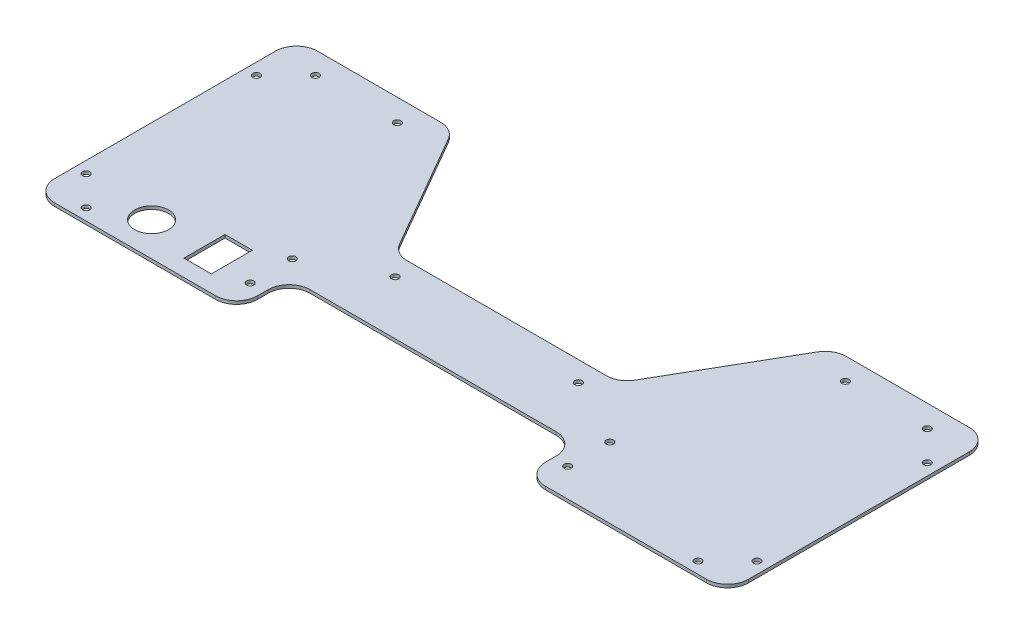
SolidWorks part; units mm, degrees
material "Alliage 1060"
ref_plane "Front" through (0, 0, 0) normal (0, 0, 1) x (1, 0, 0)
ref_plane "Top" through (0, 0, 0) normal (0, 1, 0) x (1, 0, 0)
ref_plane "Right" through (0, 0, 0) normal (1, 0, 0) x (0, 0, -1)
sketch "Esquisse1" plane through (0, 0, 0) normal (0, 1, 0) x (1, 0, 0)
  line L0 (0, 0) -> (0, 120) construction
  line L1 (-165, 120) -> (165, 120) construction
  line L2 (-165, 120) -> (-165, -30) construction
  line L3 (-165, -30) -> (-68.5, -30)
  line L4 (165, 120) -> (165, -30) construction
  line L5 (-165, -30) -> (-165, 90)
  line L6 (-165, 90) -> (-93.5278, 90) construction
  line L7 (-93.5278, 90) -> (-56, 25) construction
  line L8 (-56, 25) -> (56, 25) construction
  line L9 (56, 25) -> (93.5278, 90) construction
  line L10 (93.5278, 90) -> (165, 90) construction
  line L11 (165, 90) -> (165, -30)
  line L12 (-68.5, -30) -> (-68.5, -5)
  line L13 (-68.5, -5) -> (68.5, -5)
  line L14 (68.5, -5) -> (68.5, -30)
  line L15 (68.5, -30) -> (165, -30)
  line L16 (-165, 90) -> (-165, 95)
  line L17 (-165, 95) -> (-90.641, 95)
  line L18 (-90.641, 95) -> (-53.1132, 30)
  line L19 (-53.1132, 30) -> (53.1132, 30)
  line L20 (53.1132, 30) -> (90.641, 95)
  line L21 (90.641, 95) -> (165, 95)
  line L22 (165, 95) -> (165, 90)
  line L23 (-93.5278, 90) -> (-93.5278, 95) construction
  line L24 (-93.5278, 90) -> (-89.1976, 92.5) construction
  line L25 (-53.1132, 30) -> (-53.1132, 25) construction
  point P7 (0, 25)
  point P16 (0, -5)
  dimension "D1" = 120
  dimension "D5" = 30
  dimension "D2" = 120
  dimension "D3" = 330
  dimension "D4" = 150
  dimension "D6" = 65
  dimension "D7" = 56
  dimension "D8" = 25
  dimension "D9" = 137
  dimension "D10" = 5
extrude "Boss.-Extru.1" add sketch "Esquisse1" along normal blind 1.5
fillet "Congé2" radius 10 12 edges at (-165, 0.75, 30) (68.5, 0.75, 30) (68.5, 0.75, 5) (-68.5, 0.75, 5) (-68.5, 0.75, 30) (165, 0.75, 30) (90.641, 0.75, -95) (165, 0.75, -95) (53.1132, 0.75, -30) (-53.1132, 0.75, -30) (-90.641, 0.75, -95) (-165, 0.75, -95)
hole_wizard "Dégagement M31" positions "Esquisse2" profile "Esquisse3" hole size "M3" standard "Ansi Metric" end condition through all
sketch "Esquisse2" plane through (0, 1.5, 0) normal (0, 1, 0) x (1, 0, 0)
  line L1 (-155, -30) -> (-78.5, -30) construction
  line L2 (-165, 85) -> (-165, -20) construction
  line L3 (-75.5, -16.5) -> (-75.5, 3.5) construction
  line L4 (0, -50) -> (0, 50) construction
  line L5 (-145.5, -30) -> (-145.5, -24.5) construction
  line L6 (-145.5, -24.5) -> (-159.5, -10.5) construction
  line L7 (-159.5, -10.5) -> (-165, -10.5) construction
  line L9 (-165, 70.5) -> (-159.5, 70.5) construction
  line L10 (-159.5, 70.5) -> (-145.5, 84.5) construction
  line L11 (-145.5, 84.5) -> (-145.5, 90) construction
  line L17 (-106.53, 84.5) -> (-145.5, 84.5) construction
  point P0 (-75.5, -16.5)
  point P12 (-75.5, 3.5)
  point P22 (75.5, -16.5)
  point P23 (75.5, 3.5)
  point P26 (-145.5, -24.5)
  point P28 (-159.5, -10.5)
  point P34 (-159.5, 70.5)
  point P36 (-145.5, 84.5)
  point P52 (145.5, -24.5)
  point P53 (159.5, -10.5)
  point P54 (145.5, 84.5)
  point P55 (159.5, 70.5)
  point P56 (-43.58, 20.5)
  point P77 (43.58, 20.5)
  point P85 (-106.53, 84.5)
  point P101 (106.53, 84.5)
  dimension "D1" = 13.5
  dimension "D2" = 89.5
  dimension "D3" = 20
  dimension "D4" = 135
  dimension "D5" = 5.5
  dimension "D6" = 19.5
  dimension "D7" = 120
  dimension "D8" = 50.5
  dimension "D9" = 121.42
  dimension "D14" = 58.47
sketch "Esquisse3" plane through (-75.5, 1.5, 16.5) normal (1, 0, 0) x (0, 0, 1)
  line L0 (0, 0) -> (0, 1.5)
  line L1 (0, 1.5) -> (1.7, 1.5)
  line L2 (1.7, 1.5) -> (1.7, 0)
  line L5 (1.7, 0) -> (0, 0)
  line L11 (0, -6.35) -> (0, 107.95) construction
  dimension "Diamètre du perçage jusqu'au prochain" = 3.4
  dimension "Profondeur du perçage jusqu'au prochain" = 1.5
sketch "Esquisse4" plane through (0, 1.5, 0) normal (0, 1, 0) x (1, 0, 0)
  line L0 (-101.5, -2.5) -> (-88.5, -22) construction
  line L1 (-101.5, -2.5) -> (-88.5, -2.5)
  line L2 (-101.5, -2.5) -> (-101.5, -22)
  line L3 (-101.5, -22) -> (-88.5, -22)
  line L4 (-88.5, -2.5) -> (-88.5, -22)
  line L5 (-155, -30) -> (-78.5, -30) construction
  line L7 (-68.5, -20) -> (-68.5, -15) construction
  circle A0 centre (-125, -13.9) radius 8.1
  point P12 (-95, -12.25)
  dimension "D3" = 16.2
  dimension "D1" = 13
  dimension "D2" = 19.5
  dimension "D4" = 30
  dimension "D5" = 8
  dimension "D6" = 20
extrude "Enlèv. mat.-Extru.1" cut sketch "Esquisse4" against normal through all
